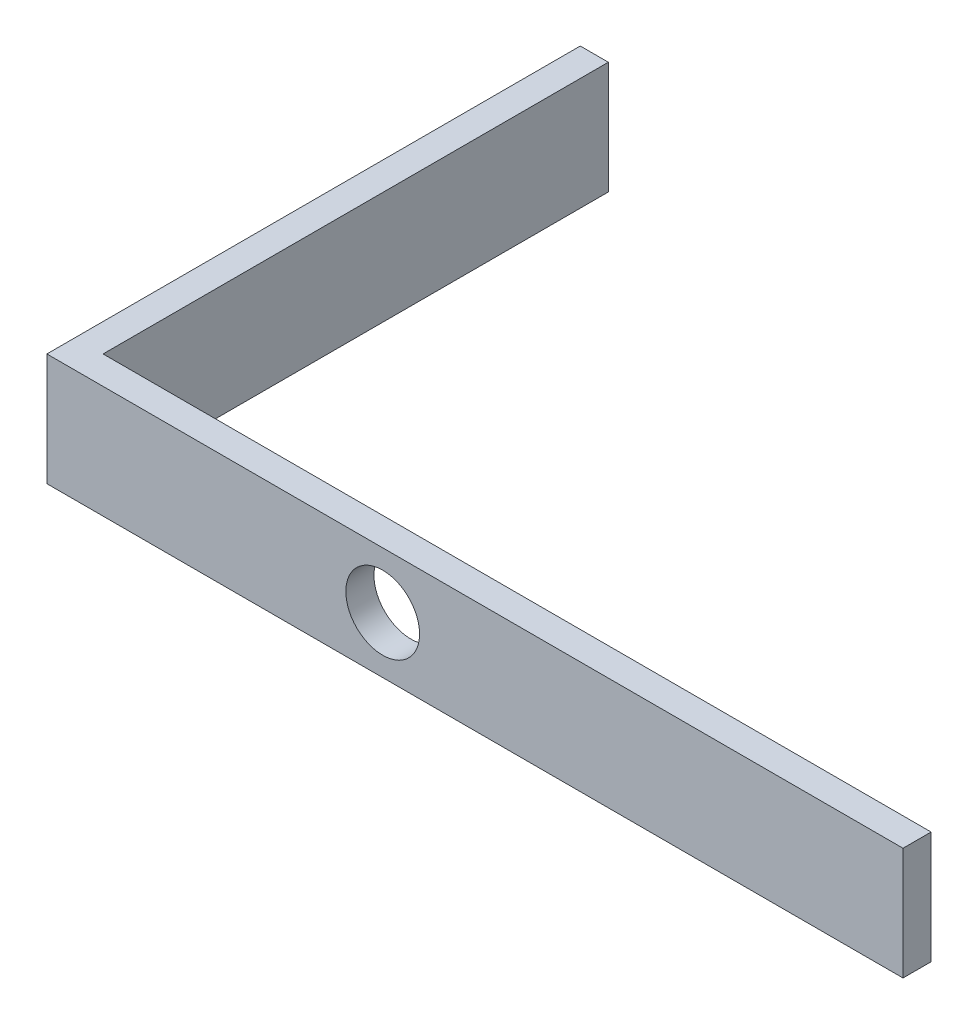
SolidWorks part; units mm, degrees
ref_plane "Front Plane" through (0, 0, 0) normal (0, 0, 1) x (1, 0, 0)
ref_plane "Top Plane" through (0, 0, 0) normal (0, 1, 0) x (1, 0, 0)
ref_plane "Right Plane" through (0, 0, 0) normal (1, 0, 0) x (0, 0, -1)
sketch "Sketch1" plane through (0, 0, 0) normal (0, 1, 0) x (1, 0, 0)
  line L1 (0, 0) -> (3.9688, 0)
  line L2 (0, 0) -> (0, 75.3427)
  line L3 (0, 75.3427) -> (3.9688, 75.3427)
  line L4 (3.9688, 3.9688) -> (3.9688, 75.3427)
  line L5 (3.9688, 0) -> (120.9358, 0)
  line L7 (3.9688, 3.9688) -> (120.9358, 3.9688)
  line L8 (120.9358, 0) -> (120.9358, 3.9688)
  dimension "D1" = 3.9688
  dimension "D2" = 3.9688
  dimension "D3" = 71.374
  dimension "D4" = 116.967
extrude "Boss-Extrude1" add sketch "Sketch1" along normal mid plane 15.875
sketch "Sketch2" plane through (0, 0, 0) normal (0, 0, 1) x (1, 0, 0)
  line L0 (0, 7.9375) -> (0, -7.9375) construction
  circle A0 centre (47.4345, 0) radius 5.207
  dimension "D1" = 47.4345
  dimension "D2" = 10.414
extrude "Cut-Extrude1" cut sketch "Sketch2" against normal up to surface (3.9688 mm away) up to face at (62.4522, 0, -3.9688)
